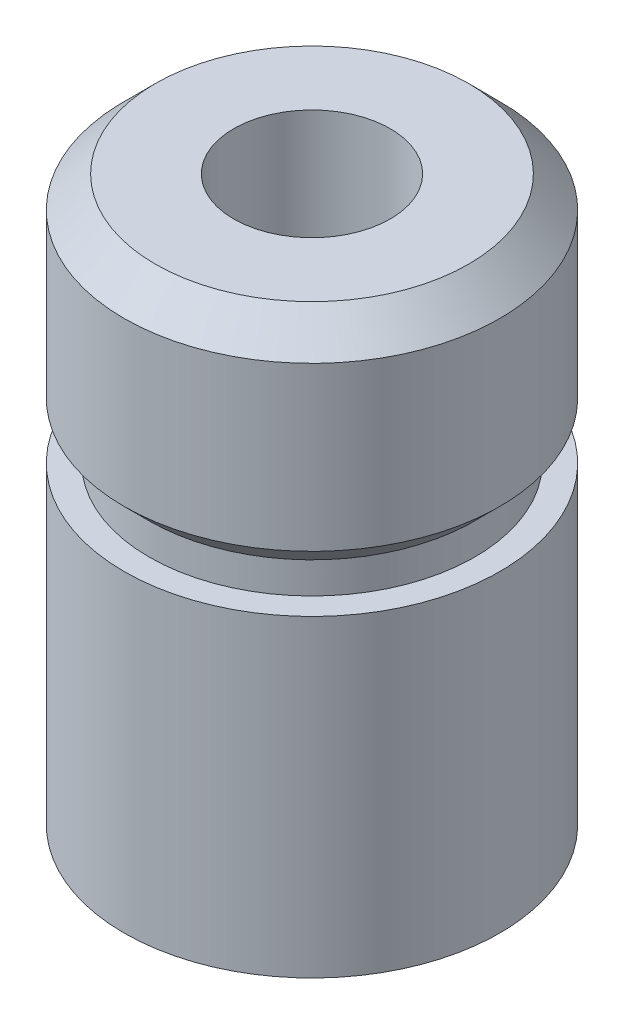
SolidWorks part; units mm, degrees
material "Brass"
ref_plane "Front Plane" through (0, 0, 0) normal (0, 0, 1) x (1, 0, 0)
ref_plane "Top Plane" through (0, 0, 0) normal (0, 1, 0) x (1, 0, 0)
ref_plane "Right Plane" through (0, 0, 0) normal (1, 0, 0) x (0, 0, -1)
sketch "Sketch1" plane through (0, 0, 0) normal (0, 1, 0) x (1, 0, 0)
  circle A0 centre (0, 0) radius 3
  dimension "D1" = 6
extrude "Boss-Extrude1" add sketch "Sketch1" along normal blind 9
sketch "Sketch2" plane through (0, 0, 0) normal (0, 0, 1) x (1, 0, 0)
  line L0 (3, 5) -> (2.6, 5)
  line L1 (2.6, 5) -> (2.6, 5.5)
  line L2 (2.6, 5.5) -> (3, 5.5)
  line L3 (3, 5.5) -> (3, 5)
  line L4 (3, 9) -> (-3, 9) construction
  line L5 (3, 0) -> (3, 9) construction
  dimension "D1" = 4
  dimension "D2" = 0.5
  dimension "D3" = 0.4
revolve "Cut-Revolve1" cut sketch "Sketch2" angle 360
chamfer "Chamfer1" distance 0.5 distance2 0.5 1 edges at (0, 9, 3)
sketch "Sketch3" plane through (0, 9, 0) normal (0, 1, 0) x (1, 0, 0)
  circle A0 centre (0, 0) radius 1.25
  dimension "D1" = 2.5
extrude "Cut-Extrude1" cut sketch "Sketch3" against normal through all
cosmetic thread "Cosmetic Thread1" parameters "D2"=3
chamfer "Chamfer2" distance 0.4 angle 45 1 edges at (0, 5.5, 3)
sketch "Sketch4" plane through (0, 5, 0) normal (0, 1, 0) x (1, 0, 0)
  line L0 (0, 0) -> (0, 50000) construction
  line L1 (-0.226, 2.9915) -> (0, 2.6)
  line L2 (0, 2.6) -> (0.226, 2.9915)
  circle A0 centre (0, 0) radius 3 construction
  circle A1 centre (0, 0) radius 2.6 construction
  arc A2 (0.226, 2.9915) -> (-0.226, 2.9915) centre (0, 0) ccw
  dimension "D1" = 60
extrude "Cut-Extrude2" cut sketch "Sketch4" along normal up to next
chamfer "Chamfer3" distance 0.05 distance2 0.05 1 edges at (0, 7.2, -2.6)
